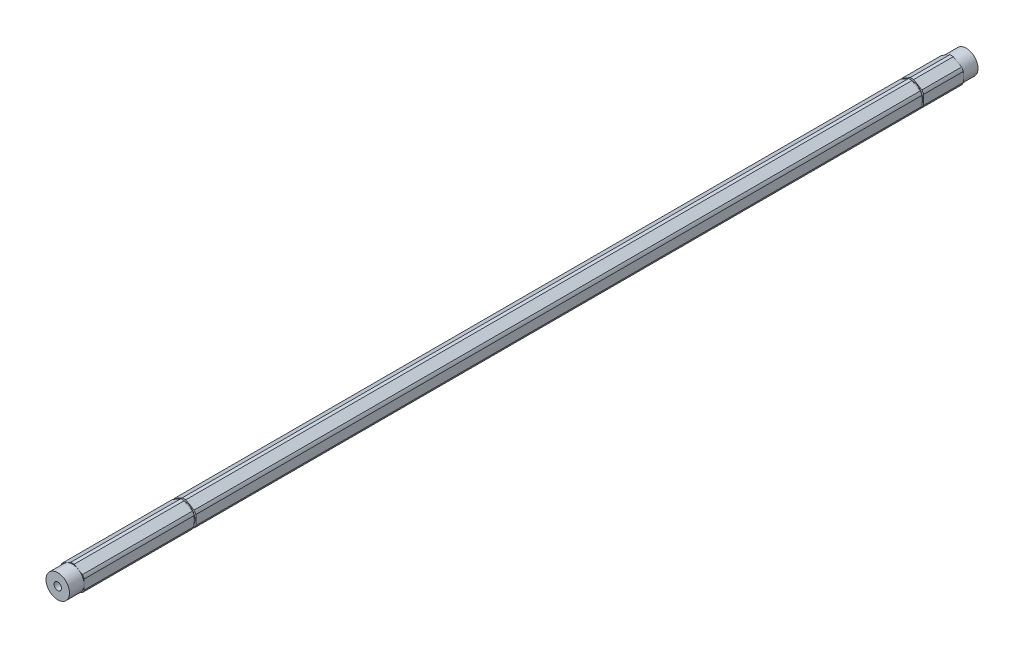
SolidWorks part; units mm, degrees
material "6061-T6 (SS)"
ref_plane "Front Plane" through (0, 0, 0) normal (0, 0, 1) x (1, 0, 0)
ref_plane "Top Plane" through (0, 0, 0) normal (0, 1, 0) x (1, 0, 0)
ref_plane "Right Plane" through (0, 0, 0) normal (1, 0, 0) x (0, 0, -1)
sketch "Sketch1" plane through (0, 0, 0) normal (0, 0, 1) x (1, 0, 0)
  line L1 (0, 7.3323) -> (-6.35, 3.6662)
  line L2 (-6.35, 3.6662) -> (-6.35, -3.6662)
  line L3 (-6.35, -3.6662) -> (0, -7.3323)
  line L4 (0, -7.3323) -> (6.35, -3.6662)
  line L5 (6.35, -3.6662) -> (6.35, 3.6662)
  line L6 (6.35, 3.6662) -> (0, 7.3323)
  circle A0 centre (0, 0) radius 6.35 construction
  circle A1 centre (0, 0) radius 2
  circle A2 centre (0, 0) radius 6.858
  dimension "D1" = 12.7
  dimension "D2" = 4
  dimension "D3" = 13.716
extrude "Boss-Extrude1" add sketch "Sketch1" along normal mid plane 474.9597 contours L5 A2 L6 L1 L2 L3 L4 A1 region at (0, 6.6711, 0)
sketch "Sketch3" plane through (0, 0, 237.4798) normal (0, 0, 1) x (1, 0, 0)
  circle A0 centre (0, 0) radius 6.35
  circle A1 centre (0, 0) radius 2
  circle A2 centre (0, 0) radius 5.8547 construction
  point P5 (0, 5.8547)
  dimension "D1" = 12.7
  dimension "D2" = 4
  dimension "D3" = 11.7094
extrude "Boss-Extrude3" add sketch "Sketch3" along normal blind 7.9375
mirror "Mirror1" about plane through (0, 0, 0) normal (0, 0, 1) of "Boss-Extrude3"
sketch "Sketch5" plane through (0, 0, 0) normal (1, 0, 0) x (0, 0, -1)
  line L0 (-237.4798, 5.8547) -> (-177.1548, 5.8547) construction
  line L1 (-178.0438, 6.858) -> (-177.1548, 6.858)
  line L2 (-178.0438, 6.858) -> (-178.0438, 5.8547)
  line L3 (-178.0438, 5.8547) -> (-177.1548, 5.8547)
  line L4 (-177.1548, 6.858) -> (-177.1548, 5.8547)
  line L5 (-237.4798, 5.8547) -> (-237.4798, -5.8547) construction
  line L6 (215.1583, 6.858) -> (216.0473, 6.858)
  line L7 (215.1583, 6.858) -> (215.1583, 5.8547)
  line L8 (0, 0) -> (14.4053, 0) construction
  line L9 (215.1583, 5.8547) -> (216.0473, 5.8547)
  line L10 (216.0473, 6.858) -> (216.0473, 5.8547)
  line L11 (237.4798, 6.7944) -> (237.4798, 6.858) construction
  point P15 (-169.6232, 7.2946)
  point P16 (-167.0995, 6.858)
  dimension "D1" = 0.889
  dimension "D2" = 6.858
  dimension "D3" = 59.436
  dimension "D4" = 0.889
  dimension "D5" = 21.4325
revolve "Cut-Revolve1" cut sketch "Sketch5" angle 360 about L8
equation "\"D2@Sketch1\"=4mm"
